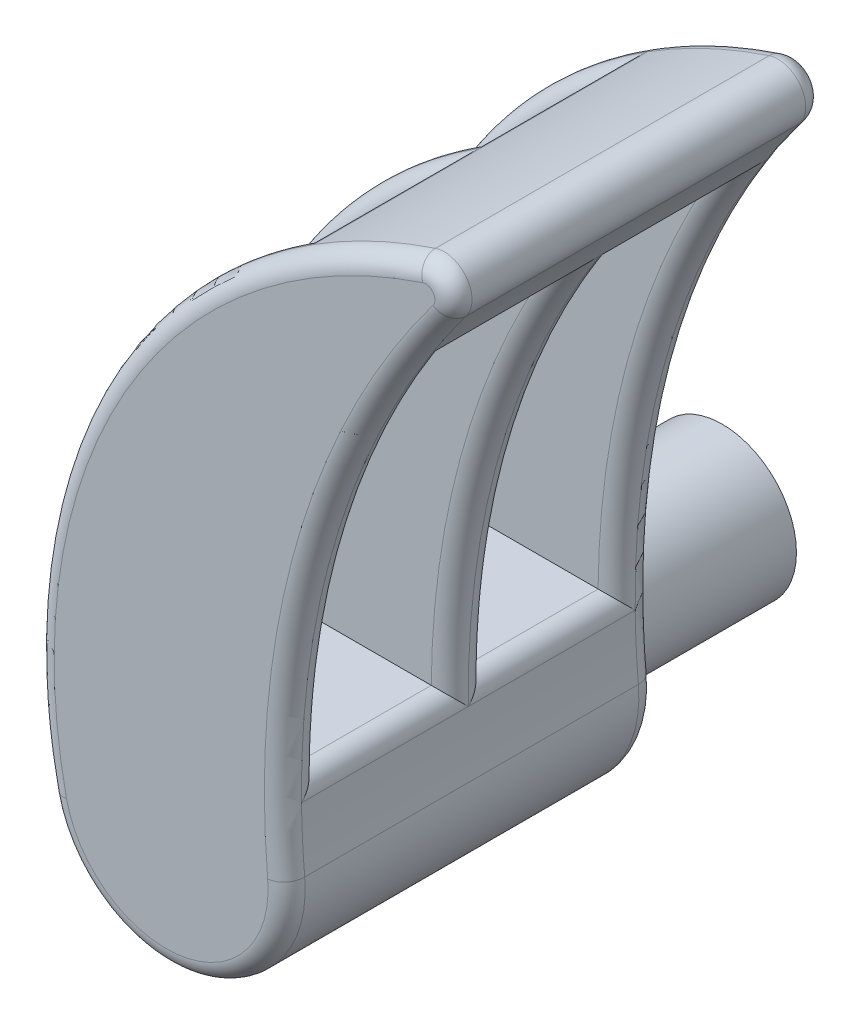
SolidWorks part; units mm, degrees
material "Aluminum 6061-T6"
ref_plane "Front Plane" through (0, 0, 0) normal (0, 0, 1) x (1, 0, 0)
ref_plane "Top Plane" through (0, 0, 0) normal (0, 1, 0) x (1, 0, 0)
ref_plane "Right Plane" through (0, 0, 0) normal (1, 0, 0) x (0, 0, -1)
sketch "Sketch1" plane through (0, 0, 0) normal (0, 0, 1) x (1, 0, 0)
  circle A0 centre (0, 0) radius 2
  dimension "D1" = 4
extrude "Boss-Extrude1" add sketch "Sketch1" along normal blind 5
sketch "Sketch2" plane through (0, 0, 5) normal (0, 0, 1) x (1, 0, 0)
  circle A0 centre (0, 0) radius 3.25
  dimension "D1" = 6.5
sketch "Sketch3" plane through (0, 0, 5) normal (0, 0, 1) x (1, 0, 0)
  line L0 (0, 0) -> (3.25, 0) construction
  arc A0 (6.7642, 16.7391) -> (-3.1756, -0.6915) centre (11.481, 2.5) ccw
  circle A1 centre (0, 0) radius 3.25 construction
  arc A2 (7.5992, 15.576) -> (6.7642, 16.7391) centre (7, 16.0271) ccw
  arc A3 (7.5992, 15.576) -> (3.237, 0.2902) centre (25.2775, 2.2658) ccw
  arc A4 (-3.1756, -0.6915) -> (3.237, 0.2902) centre (0, 0) ccw
  dimension "D1" = 30
  dimension "D3" = 1.5
  dimension "D4" = 7
  dimension "D2" = 2.5
extrude "Boss-Extrude3" add sketch "Sketch3" along normal blind 10
sketch "Sketch5" plane through (0, 0, 0) normal (1, 0, 0) x (0, 0, -1)
  line L0 (-15, 15.576) -> (-15, 0.2902) construction
  line L1 (-14, 14.2696) -> (-10.5, 14.2696)
  line L2 (-14, 14.2696) -> (-14, 2.4744)
  line L3 (-14, 2.4744) -> (-10.5, 2.4744)
  line L4 (-10.5, 14.2696) -> (-10.5, 2.4744)
  line L5 (-9.5, 14.2696) -> (-6, 14.2696)
  line L6 (-9.5, 14.2696) -> (-9.5, 2.4744)
  line L7 (-9.5, 2.4744) -> (-6, 2.4744)
  line L8 (-6, 14.2696) -> (-6, 2.4744)
  line L10 (-5, 0.2902) -> (-5, 15.576) construction
  dimension "D1" = 1
  dimension "D2" = 1
  dimension "D3" = 1
extrude "Cut-Extrude1" cut sketch "Sketch5" along normal up to surface and the other way up to surface up to face at (4.7081, 8.1357, 10) other way up to face at (0.1225, 8.9771, 10)
fillet "Fillet3" radius 0.5 22 edges at (7.6092, 16.4645, 5) (3.9982, 8.3383, 5) (0.4918, -3.2126, 5) (7.6092, 16.4645, 15) (3.9982, 8.3383, 15) (0.4918, -3.2126, 15) (4.0815, 8.623, 10.5) (3.1496, 2.4744, 12.25) (4.0815, 8.623, 14) (4.0815, 8.623, 9.5) (3.1496, 2.4744, 7.75) (4.0815, 8.623, 6) (-2.0244, 9.0272, 6) (2.1817, 14.2696, 7.75) (-2.0244, 9.0272, 9.5) (-3.519, 2.4744, 7.75) (-3.519, 2.4744, 12.25) (2.1817, 14.2696, 12.25) (-2.0244, 9.0272, 10.5) (-2.0244, 9.0272, 14) (-1.5493, 9.9305, 5) (-1.5493, 9.9305, 15)
